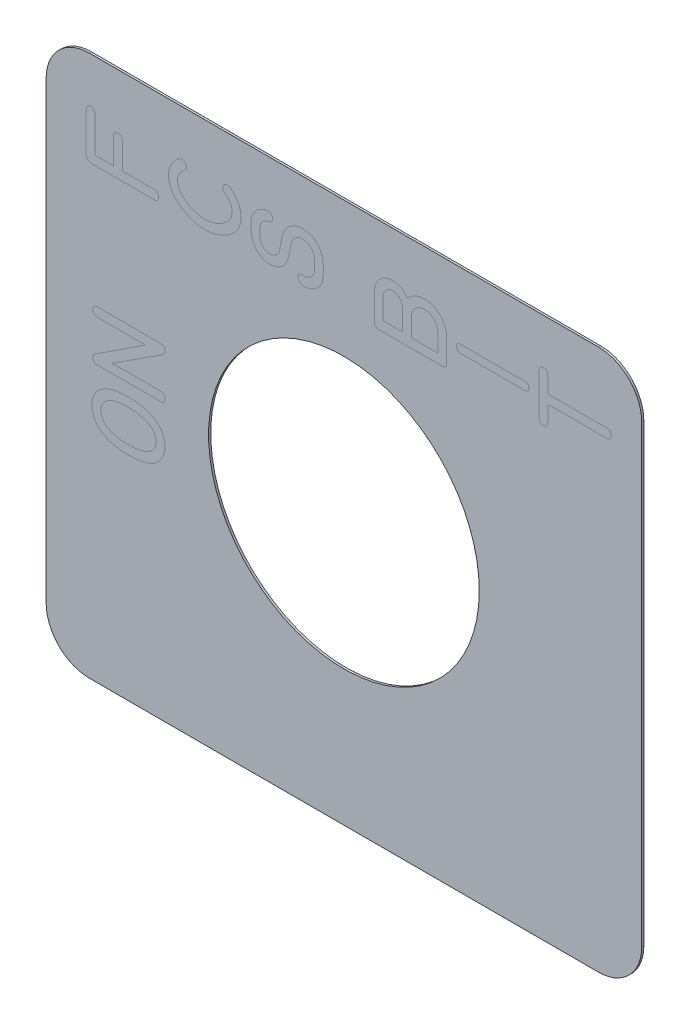
SolidWorks part; units mm, degrees
material "PET"
ref_plane "Front" through (0, 0, 0) normal (0, 0, 1) x (1, 0, 0)
ref_plane "Top" through (0, 0, 0) normal (0, 1, 0) x (1, 0, 0)
ref_plane "Right" through (0, 0, 0) normal (1, 0, 0) x (0, 0, -1)
sketch "Sketch1" plane through (0, 0, 0) normal (0, 0, 1) x (1, 0, 0)
  line L1 (-2943.5619, 6423.66) -> (-2978.4869, 6423.66)
  line L2 (-2943.5619, 6423.66) -> (-2943.5619, 6391.91)
  line L3 (-2943.5619, 6391.91) -> (-2978.4869, 6391.91)
  line L4 (-2978.4869, 6423.66) -> (-2978.4869, 6391.91)
  line L5 (-2943.5619, 6423.66) -> (-2978.4869, 6391.91) construction
  line L6 (-2943.5619, 6391.91) -> (-2978.4869, 6423.66) construction
  circle A0 centre (-2961.0244, 6407.785) radius 7.9375
  point P0 (-2961.0244, 6407.785)
  dimension "D1" = 15.875
  dimension "D2" = 31.75
  dimension "D3" = 34.925
extrude "Boss-Extrude1" add sketch "Sketch1" along normal blind 0.127
sketch "Sketch2" plane through (0, 0, 0.127) normal (0, 0, 1) x (1, 0, 0)
  line L0 (-2968.9619, 6407.785) -> (-2971.5019, 6407.785) construction
  line L3 (-2971.5019, 6400.3464) -> (-2971.5019, 6415.2236) construction
  line L5 (-2971.8829, 6423.66) -> (-2967.0569, 6423.66) construction
  line L6 (-2967.0569, 6423.66) -> (-2962.2309, 6423.66) construction
  line L7 (-2962.2309, 6423.66) -> (-2959.8179, 6423.66) construction
  line L8 (-2959.8179, 6423.66) -> (-2954.9919, 6423.66) construction
  line L9 (-2954.9919, 6423.66) -> (-2950.1659, 6423.66) construction
  line L10 (-2950.1659, 6423.66) -> (-2945.3399, 6423.66) construction
  line L11 (-2943.5619, 6423.66) -> (-2978.4869, 6423.66) construction
  line L13 (-2971.8829, 6423.66) -> (-2971.8829, 6415.6303) construction
  line L14 (-2967.0569, 6423.66) -> (-2967.0569, 6415.6303) construction
  line L15 (-2967.0569, 6415.6303) -> (-2962.2309, 6423.66) construction
  line L16 (-2962.2309, 6423.66) -> (-2962.2309, 6415.6303) construction
  line L18 (-2959.8179, 6423.66) -> (-2959.8179, 6415.6303) construction
  line L19 (-2959.8179, 6415.6303) -> (-2954.9919, 6423.66) construction
  line L20 (-2954.9919, 6423.66) -> (-2954.9919, 6415.6303) construction
  line L21 (-2954.9919, 6415.6303) -> (-2950.1659, 6423.66) construction
  line L22 (-2950.1659, 6423.66) -> (-2950.1659, 6415.6303) construction
  line L23 (-2950.1659, 6415.6303) -> (-2945.3399, 6423.66) construction
  line L24 (-2945.3399, 6423.66) -> (-2945.3399, 6415.6303) construction
  circle A0 centre (-2961.0244, 6407.785) radius 7.9375 construction
  text T0 "ON" font "GordonURWMed" height in points 18
  text T1 "F" font "GordonURWMed" height in points 18
  text T2 "C" font "GordonURWMed" height in points 18
  text T3 "S"
  text T4 "B"
  text T5 "I"
  text T6 "T"
  point P7 (-2971.5019, 6407.785)
  point P9 (-2961.0244, 6423.66)
  dimension "D1" = 2.54
  dimension "D2" = 4.826
  dimension "D3" = 2.413
wrap "Wrap1" sketch "Sketch2" wrap type scribe source sketch "Sketch2" face at (-2961.0244, 6407.785, 0.127)
fillet "Fillet1" radius 2.54 4 edges at (-2943.5619, 6391.91, 0.0635) (-2943.5619, 6423.66, 0.0635) (-2978.4869, 6423.66, 0.0635) (-2978.4869, 6391.91, 0.0635)
